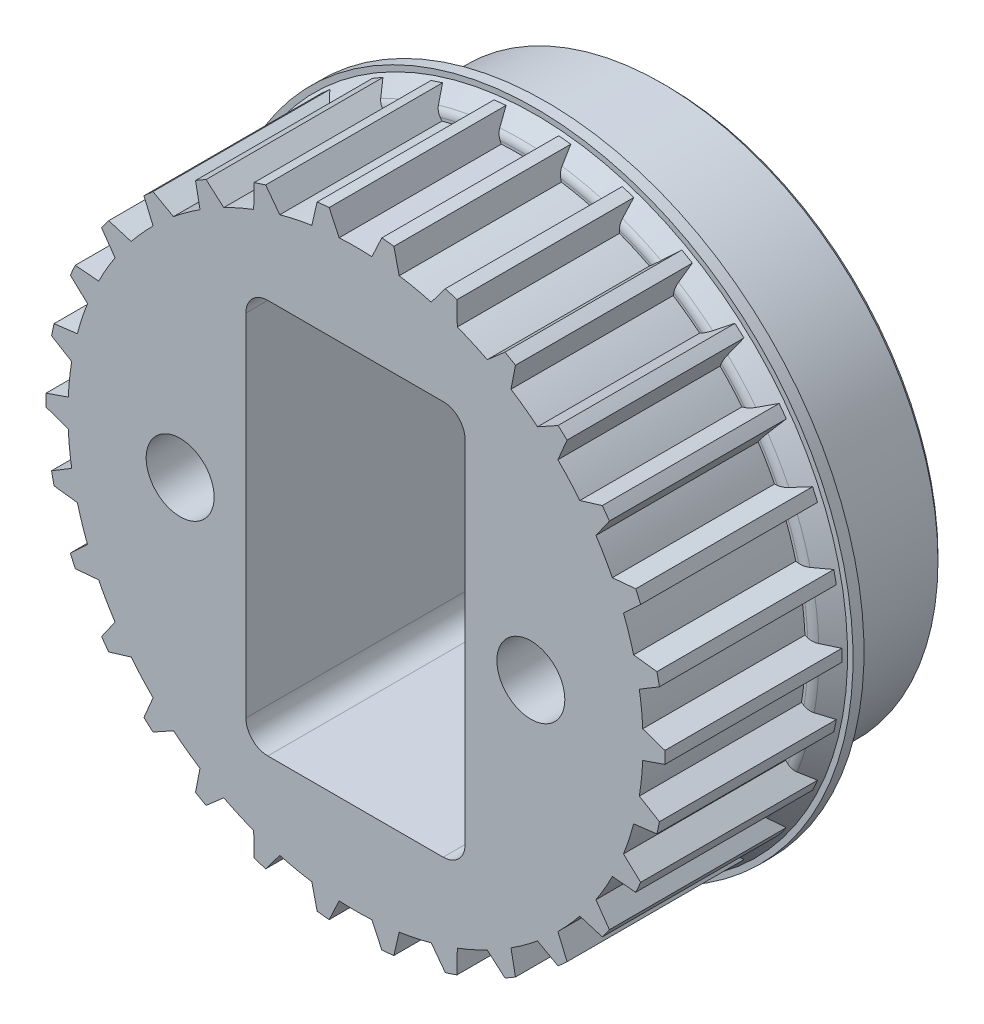
SolidWorks part; units mm, degrees
material "PMMA"
ref_plane "Ebene vorne" through (0, 0, 0) normal (0, 0, 1) x (1, 0, 0)
ref_plane "Ebene oben" through (0, 0, 0) normal (0, 1, 0) x (1, 0, 0)
ref_plane "Ebene rechts" through (0, 0, 0) normal (1, 0, 0) x (0, 0, -1)
ref_axis "Achse1" through (0, 0, 9.02) along (0, 0, -1)
sketch "Skizze1" plane through (0, 0, 0) normal (1, 0, 0) x (0, 0, -1)
  line L0 (0, 47.6717) -> (0, -53.1541) construction
  line L1 (-46.5152, 0) -> (56.3665, 0) construction
  line L2 (-4.35, 14.12) -> (4.35, 14.12)
  line L3 (4.35, 14.12) -> (4.35, 12.575)
  line L4 (4.35, 12.575) -> (9.85, 12.575)
  line L5 (9.85, 12.575) -> (9.85, 0)
  line L9 (-4.35, 14.12) -> (-4.35, 12.575)
  line L10 (-4.35, 12.575) -> (-4.35, 0)
  line L11 (-4.35, 0) -> (9.85, 0)
  point P12 (0, 0)
  point P15 (0, 14.12)
  dimension "D1" = 5.5
  dimension "D3" = 28.24
  dimension "D4" = 8.7
revolve "Rotation1" add sketch "Skizze1" angle 360 about L1
sketch "Skizze2" plane through (0, 0, 0) normal (0, 0, 1) x (1, 0, 0)
  line L0 (0, 30.4501) -> (0, -26.4561) construction
  line L1 (-21.1101, 0) -> (22.7837, 0) construction
  line L2 (-1.2, 14.0689) -> (-0.7476, 13.0987)
  line L3 (1.2, 14.0689) -> (0.7476, 13.0987)
  circle A0 centre (0, 0) radius 13.12 construction
  circle A1 centre (0, 0) radius 14.12 construction
  circle A2 centre (0, 0) radius 14.12 construction
  arc A3 (-1.2, 14.0689) -> (1.2, 14.0689) centre (0, 0) cw
  arc A4 (-0.7476, 13.0987) -> (0.7476, 13.0987) centre (0, 0) cw
  dimension "D1" = 28.24
  dimension "D2" = 26.24
  dimension "D6" = 1
  dimension "D3" = 50
  dimension "D4" = 2.4
  dimension "D5" = 1.4951
extrude "Schnitt-Linear austragen1" cut sketch "Skizze2" against normal through all and the other way through all
pattern_circular "Kreismuster1" count 30 over 360 about axis through (0, 0, 9.02) along (0, 0, -1) of "Schnitt-Linear austragen1"
sketch "Skizze3" plane through (0, 0, 0) normal (1, 0, 0) x (0, 0, -1)
  line L0 (4.35, 13) -> (4.35, 14.5)
  line L1 (4.35, 14.5) -> (3.85, 14.5)
  line L2 (3.85, 14.5) -> (3.85, 14.25)
  line L3 (3.85, 14.25) -> (3.1964, 13.5964)
  line L4 (3.05, 13.2429) -> (3.05, 13)
  line L5 (3.05, 13) -> (4.35, 13)
  line L6 (4.35, 13.0987) -> (4.35, 14.0689) construction
  line L7 (0, 19.3181) -> (0, -13.1661) construction
  line L8 (11.0313, 0) -> (-11.7934, 0) construction
  arc A0 (3.05, 13.2429) -> (3.1964, 13.5964) centre (3.55, 13.2429) cw
  dimension "D7" = 0.5
  dimension "D1" = 14.5
  dimension "D2" = 13
  dimension "D3" = 0.5
  dimension "D4" = 14.25
  dimension "D5" = 45
  dimension "D6" = 0.8
revolve "Rotation2" add sketch "Skizze3" angle 360 about L8
sketch "Skizze4" plane through (0, 0, 0) normal (0, 0, 1) x (1, 0, 0)
  line L0 (0, 24.4145) -> (0, -17.917) construction
  line L1 (-17.7015, 0) -> (18.3014, 0) construction
  line L2 (4, 9) -> (-4, 9)
  line L3 (-5, 8) -> (-5, -8)
  line L4 (5, 8) -> (5, -8)
  line L5 (4, -9) -> (-4, -9)
  arc A0 (-5, 8) -> (-4, 9) centre (-4, 8) cw
  arc A1 (5, 8) -> (4, 9) centre (4, 8) ccw
  arc A2 (5, -8) -> (4, -9) centre (4, -8) cw
  arc A3 (-5, -8) -> (-4, -9) centre (-4, -8) ccw
  circle A4 centre (-8, 0) radius 1.55
  circle A5 centre (8, 0) radius 1.55
  point P13 (-5, 0)
  point P14 (0, 9)
  point P20 (0, -9)
  point P21 (5, 0)
  dimension "D1" = 1
  dimension "D4" = 3.1
  dimension "D2" = 18
  dimension "D3" = 10
  dimension "D5" = 16
extrude "Schnitt-Linear austragen2" cut sketch "Skizze4" against normal through all and the other way through all
fillet "Verrundung1" radius 1.2 8 edges at (-4.7071, 8.7071, -9.85) (0, 9, -9.85) (4.7071, 8.7071, -9.85) (5, 0, -9.85) (4.7071, -8.7071, -9.85) (0, -9, -9.85) (-4.7071, -8.7071, -9.85) (-5, 0, -9.85)
chamfer "Fase1" distance 0.2 angle 45 3 edges at (-6.45, 0, -9.85) (6.45, 0, -9.85) (12.575, 0, -9.85)
